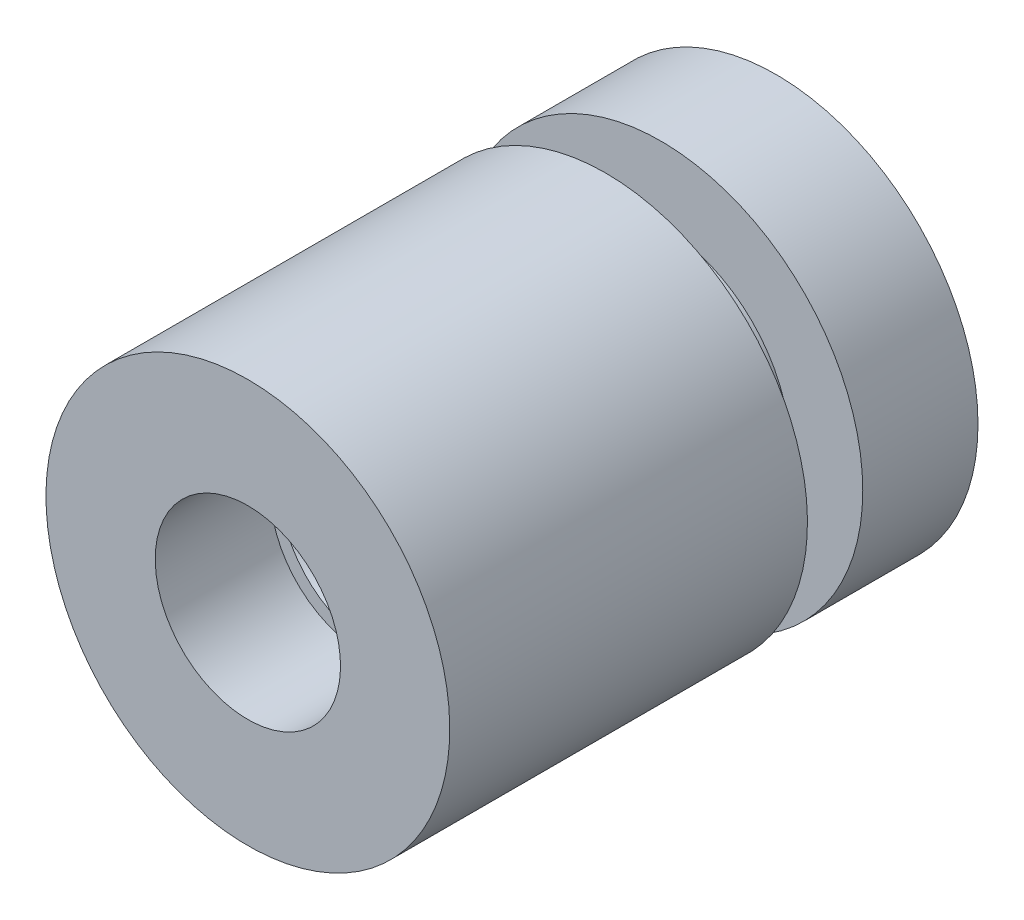
SolidWorks part; units mm, degrees
ref_plane "Front Plane" through (0, 0, 0) normal (0, 0, 1) x (1, 0, 0)
ref_plane "Top Plane" through (0, 0, 0) normal (0, 1, 0) x (1, 0, 0)
ref_plane "Right Plane" through (0, 0, 0) normal (1, 0, 0) x (0, 0, -1)
sketch "Sketch1" plane through (0, 0, 0) normal (1, 0, 0) x (0, 0, -1)
  line L1 (0, 5.5626) -> (-3.175, 5.5626)
  line L2 (-3.175, 5.5626) -> (-3.175, 3.556)
  line L3 (-3.175, 3.556) -> (-11.1252, 3.556)
  line L4 (-11.1252, 3.556) -> (-11.1252, 0)
  line L5 (-11.1252, 0) -> (-1.016, 0)
  line L8 (3.096, 0) -> (10.0173, 0) construction
  arc A0 (0, 5.5626) -> (-1.016, 0) centre (11.6718, 0.5567) ccw
  dimension "D7" = 12.7
  dimension "D1" = 7.112
  dimension "D2" = 11.1252
  dimension "D3" = 3.175
  dimension "D4" = 2.0066
  dimension "D5" = 11.1252
  dimension "D6" = 7.9502
  dimension "D8" = 10.1092
revolve "Revolve1" add sketch "Sketch1" angle 360 about L8
hole_wizard "#10-32 Tapped Hole1" positions "Sketch3" profile "Sketch2" tap size "#10-32" standard "ANSI Inch" end condition up to next
sketch "Sketch3" plane through (0, 0, 11.1252) normal (0, 0, 1) x (1, 0, 0)
  point P0 (0, 0)
sketch "Sketch2" plane through (0, 0, 11.1252) normal (1, 0, 0) x (0, -1, 0)
  line L0 (0, 0) -> (0, 10.1092)
  line L1 (0, 10.1092) -> (2.54, 10.1092)
  line L2 (2.0193, 9.5885) -> (2.0193, 0.5207)
  line L3 (2.0193, 0.5207) -> (2.54, 0)
  line L5 (2.54, 0) -> (0, 0)
  line L6 (-2.0193, 0.5207) -> (-2.54, 0) construction
  line L7 (2.54, 10.1092) -> (2.0193, 9.5885)
  line L8 (-2.54, 10.1092) -> (-2.0193, 9.5885) construction
  line L11 (0, -6.35) -> (0, 107.95) construction
  dimension "Thread Major Dia." = 4.0386
  dimension "Thru Tap Drill Depth" = 10.1092
  dimension "Near C'Sink Dia." = 5.08
  dimension "Near C'Sink Angle" = 90
  dimension "Far C'Sink Dia." = 5.08
  dimension "Far C'Sink Angle" = 90
sketch "Sketch4" plane through (0, 0, 0) normal (1, 0, 0) x (0, 0, -1)
  line L0 (-4.699, 3.6195) -> (-4.699, 5.5626)
  line L1 (-4.699, 5.5626) -> (-14.5542, 5.5626)
  line L2 (-14.5542, 5.5626) -> (-14.5542, 2.5527)
  line L3 (-14.5542, 2.5527) -> (-11.3792, 2.5527)
  line L4 (-11.3792, 2.5527) -> (-11.3792, 3.6195)
  line L5 (-11.3792, 3.6195) -> (-4.699, 3.6195)
  line L6 (-18.7386, 0) -> (-26.221, 0) construction
  line L7 (-3.175, 5.5626) -> (-3.175, 3.556) construction
  dimension "D1" = 1.524
  dimension "D2" = 5.1054
  dimension "D3" = 0.254
  dimension "D4" = 6.6802
  dimension "D5" = 11.1252
  dimension "D6" = 3.175
  dimension "D7" = 7.239
revolve "Revolve2" add sketch "Sketch4" angle 360 about L6
